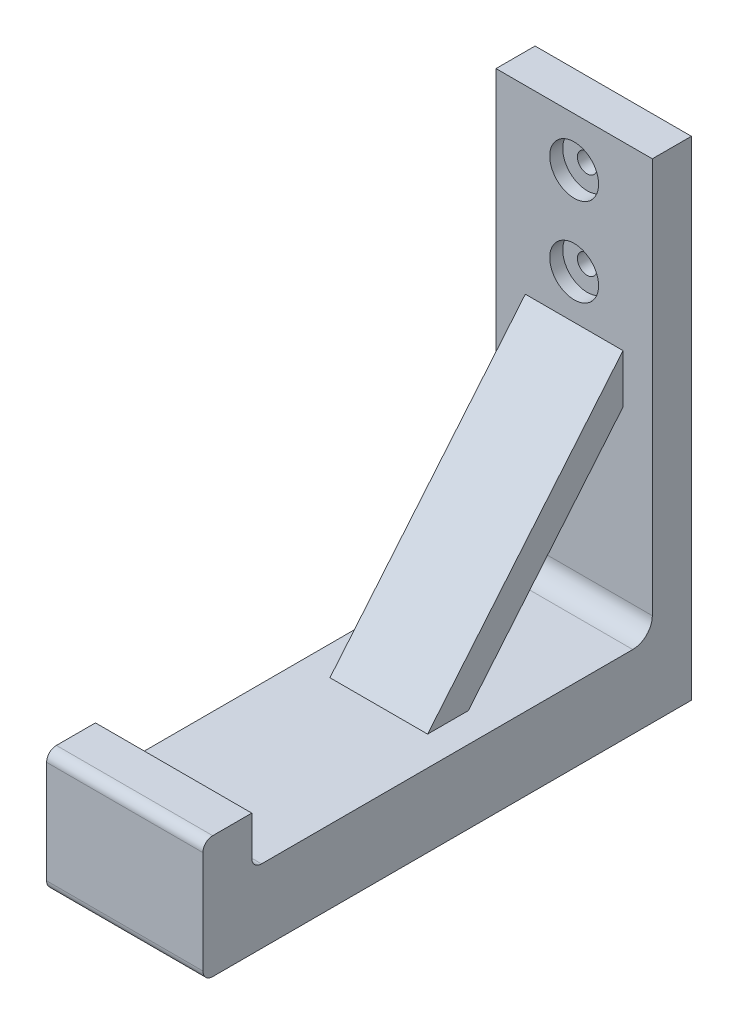
SolidWorks part; units mm, degrees
ref_plane "Front Plane" through (0, 0, 0) normal (0, 0, 1) x (1, 0, 0)
ref_plane "Top Plane" through (0, 0, 0) normal (0, 1, 0) x (1, 0, 0)
ref_plane "Right Plane" through (0, 0, 0) normal (1, 0, 0) x (0, 0, -1)
sketch "Sketch1" plane through (0, 0, 0) normal (1, 0, 0) x (0, 0, -1)
  line L0 (0, 0) -> (0, 127)
  line L5 (0, 127) -> (-10.16, 127)
  line L6 (-10.16, 127) -> (-10.16, 19.05)
  line L11 (-10.16, 19.05) -> (-114.3, 19.05)
  line L12 (-114.3, 19.05) -> (-114.3, 31.75)
  line L13 (-114.3, 31.75) -> (-127, 31.75)
  line L14 (-127, 31.75) -> (-127, 0)
  line L15 (-127, 0) -> (0, 0)
  line L16 (-60.96, 19.05) -> (-10.16, 80.01)
  line L17 (-50.3767, 19.05) -> (-10.16, 67.31)
  line L18 (-60.96, 19.05) -> (-50.3767, 19.05)
  line L19 (-10.16, 67.31) -> (-10.16, 80.01)
  dimension "D1" = 127
  dimension "D2" = 127
  dimension "D3" = 10.16
  dimension "D4" = 12.7
  dimension "D5" = 19.05
  dimension "D6" = 12.7
  dimension "D7" = 50.8
  dimension "D8" = 60.96
  dimension "D10" = 12.7
extrude "Boss-Extrude1" add sketch "Sketch1" along normal mid plane 40.64 contours L0 L5 L6 L11 L12 L13 L14 L15
extrude "Boss-Extrude2" add sketch "Sketch1<9>" along normal mid plane 25.4 contours L16 L19 L17 L18
sketch "Sketch1<9>" plane through (0, 0, 0) normal (1, 0, 0) x (0, 0, -1) same geometry as "Sketch1"
hole_wizard "CBORE for #10 Pan Head Machine Screw1" positions "Sketch2" profile "Sketch3" counterbore size "#10" standard "ANSI Inch" end condition through all
sketch "Sketch2" plane through (0, 0, 10.16) normal (0, 0, 1) x (1, 0, 0)
  line L0 (-20.32, 127) -> (-20.32, 19.05) construction
  line L1 (20.32, 127) -> (-20.32, 127) construction
  point P0 (0, 91.44)
  point P2 (0, 114.3)
  dimension "D1" = 20.32
  dimension "D2" = 20.32
  dimension "D3" = 12.7
  dimension "D4" = 35.56
sketch "Sketch3" plane through (0, 91.44, 10.16) normal (1, 0, 0) x (0, -1, 0)
  line L0 (0, 0) -> (0, 10.16)
  line L1 (0, 10.16) -> (2.54, 10.16)
  line L3 (2.54, 10.16) -> (2.54, 3.3782)
  line L4 (2.54, 3.3782) -> (6.35, 3.3782)
  line L5 (6.35, 3.3782) -> (6.35, 0)
  line L7 (6.35, 0) -> (0, 0)
  line L11 (0, -6.35) -> (0, 107.95) construction
  dimension "Thru Hole Dia." = 5.08
  dimension "Thru Hole Depth" = 10.16
  dimension "C'Bore Dia." = 12.7
  dimension "C'Bore Depth" = 3.3782
fillet "Fillet1" radius 5.08 1 edges at (0, 19.05, 10.16)
fillet "Fillet2" radius 2.54 1 edges at (0, 19.05, 114.3)
fillet "Fillet3" radius 2.54 1 edges at (0, 0, 127)
fillet "Fillet4" radius 2.54 1 edges at (0, 31.75, 127)
